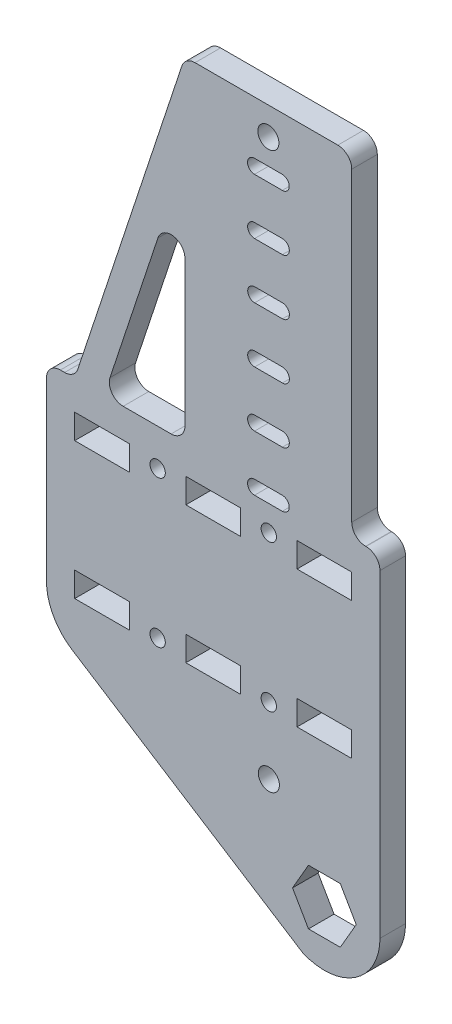
SolidWorks part; units mm, degrees
ref_plane "Front Plane" through (0, 0, 0) normal (0, 0, 1) x (1, 0, 0)
ref_plane "Top Plane" through (0, 0, 0) normal (0, 1, 0) x (1, 0, 0)
ref_plane "Right Plane" through (0, 0, 0) normal (1, 0, 0) x (0, 0, -1)
sketch "Sketch1" plane through (0, 0, 0) normal (0, 0, 1) x (1, 0, 0)
  line L0 (-38.1, 0) -> (38.1, 0) construction
  line L1 (31.65, -12.8) -> (19.15, -12.8)
  line L2 (38.1, -12.8) -> (38.1, 12.8)
  line L3 (31.65, 12.8) -> (19.15, 12.8)
  line L4 (-38.1, -12.8) -> (-38.1, 12.8)
  line L5 (38.1, -12.8) -> (-38.1, 12.8) construction
  line L6 (38.1, 12.8) -> (-38.1, -12.8) construction
  line L7 (6.25, 18.442) -> (-6.25, 18.442)
  line L8 (-19.15, -18.442) -> (-31.65, -12.8) construction
  line L9 (-19.15, -12.8) -> (-31.65, -18.442) construction
  line L10 (6.25, -12.8) -> (-6.25, -12.8)
  line L11 (-19.15, -12.8) -> (-31.65, -12.8)
  line L12 (31.65, -12.8) -> (31.65, -18.442)
  line L13 (19.15, -12.8) -> (19.15, -18.442)
  line L14 (12.6, 101.346) -> (12.6, 25.146) construction
  line L15 (-19.15, 12.8) -> (-19.15, 18.442)
  line L16 (-19.15, 18.442) -> (-31.65, 18.442)
  line L17 (-31.65, 12.8) -> (-31.65, 18.442)
  line L18 (-19.15, 12.8) -> (-31.65, 18.442) construction
  line L19 (-19.15, 18.442) -> (-31.65, 12.8) construction
  line L20 (-6.25, 12.8) -> (-6.25, 18.442)
  line L21 (6.25, 12.8) -> (6.25, 18.442)
  line L22 (31.65, 18.442) -> (19.15, 18.442)
  line L23 (19.15, 12.8) -> (19.15, 18.442)
  line L24 (31.65, 12.8) -> (31.65, 18.442)
  line L25 (-19.15, 12.8) -> (-31.65, 12.8)
  line L26 (6.25, 12.8) -> (-6.25, 12.8)
  line L27 (-38.1, 12.8) -> (-38.1, 25.146)
  line L28 (-38.1, 25.146) -> (-31.65, 25.146)
  line L29 (31.65, 25.146) -> (38.1, 25.146)
  line L30 (38.1, 25.146) -> (38.1, 12.8)
  line L31 (31.65, -18.442) -> (19.15, -18.442)
  line L32 (6.25, -12.8) -> (6.25, -18.442)
  line L33 (-6.25, -12.8) -> (-6.25, -18.442)
  line L34 (-31.65, -12.8) -> (-31.65, -18.442)
  line L35 (-19.15, -18.442) -> (-31.65, -18.442)
  line L36 (-19.15, -12.8) -> (-19.15, -18.442)
  line L37 (6.25, -18.442) -> (-6.25, -18.442)
  line L38 (31.65, -12.8) -> (19.15, -12.8)
  line L39 (-19.15, -12.8) -> (-31.65, -12.8)
  line L40 (6.25, -12.8) -> (-6.25, -12.8)
  line L41 (6.25, 12.8) -> (19.15, 12.8) construction
  line L42 (32.6746, -50.8) -> (29.0373, -44.5)
  line L43 (29.0373, -44.5) -> (21.7627, -44.5)
  line L44 (21.7627, -44.5) -> (18.1254, -50.8)
  line L45 (18.1254, -50.8) -> (21.7627, -57.1)
  line L46 (21.7627, -57.1) -> (29.0373, -57.1)
  line L47 (29.0373, -57.1) -> (32.6746, -50.8)
  line L48 (-6.25, 12.8) -> (-19.15, 12.8) construction
  line L49 (31.65, 25.146) -> (31.65, 101.346)
  line L50 (31.65, 101.346) -> (-6.45, 101.346)
  line L51 (-6.45, 101.346) -> (-31.65, 25.146)
  line L52 (-6.45, 81.122) -> (-6.45, 25.146)
  line L53 (-6.45, 25.146) -> (-24.9618, 25.146)
  line L54 (-6.45, 81.122) -> (-24.9618, 25.146)
  line L55 (-38.1, -12.8) -> (-38.1, -25.146)
  line L56 (-0.4211, 99.3522) -> (-25.6211, 23.1522) construction
  line L57 (-38.1, -25.146) -> (20.4722, -62.505)
  line L58 (38.1, -12.8) -> (38.1, -25.146)
  line L59 (38.1, -25.146) -> (38.1, -50.8)
  circle A0 centre (25.4, -50.8) radius 6.3 construction
  circle A1 centre (12.7, 16.7687) radius 1.7526
  circle A2 centre (-12.7, 16.7687) radius 1.7526
  circle A3 centre (12.7, -16.7687) radius 1.7526
  circle A4 centre (-12.7, -16.7687) radius 1.7526
  circle A5 centre (12.6, 94.996) radius 2.413
  arc A6 (20.4722, -62.505) -> (38.1, -50.8) centre (25.4, -50.8) ccw
  point P0 (0, 0)
  point P8 (-25.4, 15.621)
  point P37 (-25.4, -15.621)
  point P70 (-3.225, -28.575)
  dimension "D3" = 12.5
  dimension "D5" = 12.6
  dimension "D6" = 50.8
  dimension "D8" = 3.5052
  dimension "D13" = 3.5052
  dimension "D11" = 4.826
  dimension "D1" = 25.6
  dimension "D2" = 76.2
  dimension "D7" = 63.5
  dimension "D4" = 5.642
  dimension "D9" = 12.7
  dimension "D10" = 3
  dimension "D12" = 3.9688
  dimension "D14" = 3.9688
  dimension "D15" = 76.2
  dimension "D16" = 38.1
  dimension "D17" = 6.35
  dimension "D20" = 9.525
  dimension "D21" = 9.525
  dimension "D18" = 6.35
extrude "Boss-Extrude1" add sketch "Sketch1" along normal blind 5.842 contours L58 L2 L30 L29 L49 L50 L51 L28 L27 L4 L55 A4 L32 L37 L33 L10 L11 L36 L35 L34 L12 L31 L13 L1 L21 L26 L20 L7 L15 L25 L17 L16 L24 L3 L23 L22 L47 L46 L45 L44 region at (36.2839, -18.973, 0)
fillet "Fillet1" radius 3.175 4 edges at (-38.1, 25.146, 2.921) (38.1, 25.146, 2.921) (-31.65, 25.146, 2.921) (31.65, 25.146, 2.921)
fillet "Fillet2" radius 3.175 3 edges at (-6.45, 25.146, 2.921) (-6.45, 81.122, 2.921) (-24.9618, 25.146, 2.921)
fillet "Fillet3" radius 3.175 2 edges at (31.65, 101.346, 2.921) (-6.45, 101.346, 2.921)
sketch "Sketch2" plane through (0, 0, 5.842) normal (0, 0, 1) x (1, 0, 0)
  circle A0 centre (29.0373, -44.5) radius 0.1984
  circle A1 centre (32.6746, -50.8) radius 0.1984
  circle A2 centre (29.0373, -57.1) radius 0.1984
  circle A3 centre (21.7627, -57.1) radius 0.1984
  circle A4 centre (18.1254, -50.8) radius 0.1984
  circle A5 centre (21.7627, -44.5) radius 0.1984
  dimension "D1" = 0.3969
  dimension "D2" = 0.3969
  dimension "D3" = 0.3969
  dimension "D4" = 0.3969
  dimension "D5" = 0.3969
  dimension "D6" = 0.3969
extrude "Cut-Extrude1" [suppressed] cut sketch "Sketch2" against normal through all
sketch "Sketch3" plane through (0, 0, 5.842) normal (0, 0, 1) x (1, 0, 0)
  line L0 (12.6, 94.996) -> (12.7, -16.7687) construction
  circle A0 centre (12.7136, -32.004) radius 2.413
  dimension "D1" = 4.826
  dimension "D2" = 127
extrude "Cut-Extrude2" cut sketch "Sketch3" against normal through all
sketch "Sketch5" [suppressed] plane through (0, 0, 5.842) normal (0, 0, 1) x (1, 0, 0)
  line L1 (-55.0734, 111.0269) -> (34.825, 111.0269)
  line L2 (-55.0734, 111.0269) -> (-55.0734, 25.146)
  line L3 (-55.0734, 25.146) -> (34.825, 25.146)
  line L4 (34.825, 111.0269) -> (34.825, 25.146)
extrude "Cut-Extrude3" [suppressed] cut sketch "Sketch5" against normal through all
sketch "Sketch6" [suppressed] plane through (0, 0, 5.842) normal (0, 0, 1) x (1, 0, 0)
  line L0 (-34.925, 25.146) -> (34.925, 25.146) construction
  line L1 (31.4879, 25.146) -> (-22.4871, 25.146)
  line L2 (31.4879, 78.486) -> (34.6629, 74.676)
  line L3 (31.4879, 78.486) -> (-20.5821, 78.486)
  line L4 (-22.4871, 25.146) -> (-25.0279, 25.146)
  line L5 (34.6629, 25.146) -> (-22.4871, 78.486) construction
  line L6 (34.6629, 78.486) -> (-22.4871, 25.146) construction
  line L7 (6.0879, 25.146) -> (6.0879, 48.411) construction
  line L8 (-31.75, 25.146) -> (-22.4871, 51.816)
  line L9 (-38.1, -23.6461) -> (-38.1, 21.971) construction
  line L10 (34.6629, 74.676) -> (34.6629, 41.021)
  line L11 (-31.75, 25.146) -> (-25.0279, 25.146)
  line L12 (-22.4871, 51.816) -> (-22.4871, 71.3764)
  line L13 (31.4879, 70.866) -> (31.4879, 42.926) construction
  line L14 (31.4879, 37.846) -> (31.4879, 25.146)
  line L15 (31.4879, 37.846) -> (34.6629, 41.021)
  circle A0 centre (31.4879, 70.866) radius 1.651
  circle A1 centre (31.4879, 42.926) radius 1.651
  circle A2 centre (-20.5821, 74.676) radius 1.651
  circle A3 centre (-19.3121, 27.686) radius 1.651
  arc A4 (-20.5821, 78.486) -> (-22.4871, 71.3764) centre (-20.5821, 74.676) ccw
  point P0 (6.0879, 51.816)
  point P13 (-25.7515, 23.0626)
  point P14 (-16.4886, 49.7326)
  dimension "D5" = 3.302
  dimension "D6" = 3.302
  dimension "D9" = 12.7
  dimension "D10" = 3.302
  dimension "D12" = 3.302
  dimension "D1" = 53.34
  dimension "D2" = 57.15
  dimension "D3" = 6.35
  dimension "D7" = 49.53
  dimension "D8" = 27.94
  dimension "D11" = 52.07
  dimension "D13" = 50.8
  dimension "D14" = 15.24
  dimension "D4" = 7.62
extrude "Boss-Extrude3" [suppressed] add sketch "Sketch6" against normal up to surface (5.842 mm away) up to face at (15.1266, -32.004, 0)
fillet "Fillet6" [suppressed] radius 3.175
fillet "Fillet7" [suppressed] radius 1.5875
sketch "Sketch7" [suppressed] plane through (0, 0, 5.842) normal (0, 0, 1) x (1, 0, 0)
  line L0 (20.9561, 53.086) -> (-41.1495, 53.086) construction
  line L2 (5.0811, 78.486) -> (5.0811, 25.1147) construction
  line L3 (30.7443, 78.486) -> (-20.5821, 78.486) construction
  line L4 (5.0811, 65.786) -> (5.0811, 40.386) construction
  line L5 (8.2561, 65.786) -> (8.2561, 40.386)
  line L6 (1.9061, 65.786) -> (1.9061, 40.386)
  line L7 (17.7811, 65.786) -> (17.7811, 40.386) construction
  line L8 (20.9561, 65.786) -> (20.9561, 40.386)
  line L9 (14.6061, 65.786) -> (14.6061, 40.386)
  line L10 (-24.5007, 53.086) -> (20.9561, 53.086) construction
  line L11 (-7.6189, 65.786) -> (-7.6189, 40.386) construction
  line L12 (-10.7939, 65.786) -> (-10.7939, 40.386)
  line L13 (-4.4439, 65.786) -> (-4.4439, 40.386)
  arc A0 (8.2561, 65.786) -> (1.9061, 65.786) centre (5.0811, 65.786) ccw
  arc A1 (1.9061, 40.386) -> (8.2561, 40.386) centre (5.0811, 40.386) ccw
  arc A2 (20.9561, 65.786) -> (14.6061, 65.786) centre (17.7811, 65.786) ccw
  arc A3 (14.6061, 40.386) -> (20.9561, 40.386) centre (17.7811, 40.386) ccw
  arc A4 (-10.7939, 65.786) -> (-4.4439, 65.786) centre (-7.6189, 65.786) cw
  arc A5 (-4.4439, 40.386) -> (-10.7939, 40.386) centre (-7.6189, 40.386) cw
  point P10 (5.0811, 53.086)
  point P18 (17.7811, 53.086)
  point P26 (-7.6189, 53.086)
  dimension "D2" = 3.175
  dimension "D1" = 25.4
  dimension "D3" = 25.4
  dimension "D4" = 2
extrude "Cut-Extrude4" [suppressed] cut sketch "Sketch7" against normal through all
sketch "Sketch9" [suppressed] plane through (0, 0, 5.842) normal (0, 0, 1) x (1, 0, 0)
  line L0 (-38.1, -7.52) -> (38.1, -7.52) construction
  line L1 (-38.1, -23.6461) -> (-38.1, 21.971) construction
  line L2 (38.1, 21.971) -> (38.1, -17.5528) construction
  line L3 (-19.15, 12.8) -> (-31.65, 12.8) construction
  text T0 "SERGE" font "Roboto Condensed" height in points 42
  dimension "D1" = 20.32
extrude "Cut-Extrude5" [suppressed] cut sketch "Sketch9" against normal blind 0.3969
sketch "Sketch10" [suppressed] plane through (0, 0, 5.842) normal (0, 0, 1) x (1, 0, 0)
  line L0 (-38.1, -4.345) -> (38.1, -4.345) construction
  line L1 (-38.1, -23.6461) -> (-38.1, 21.971) construction
  line L2 (38.1, 21.971) -> (38.1, -17.5528) construction
  line L3 (-19.15, 12.8) -> (-31.65, 12.8) construction
  text T0 "SERGE" font "Bebas Neue" height in points 36
  dimension "D1" = 17.145
extrude "Cut-Extrude6" [suppressed] cut sketch "Sketch10" against normal blind 0.1984
sketch "Sketch11" plane through (0, 0, 5.842) normal (0, 0, 1) x (1, 0, 0)
  line L0 (12.6, 94.996) -> (12.7, 16.7687) construction
  line L1 (9.4669, 62.2324) -> (15.8169, 62.2324) construction
  line L2 (9.4669, 63.8199) -> (15.8169, 63.8199)
  line L3 (9.4669, 60.6449) -> (15.8169, 60.6449)
  line L4 (31.75, 55.8824) -> (-6.45, 55.8824) construction
  line L5 (-6.45, 61.4095) -> (-6.45, 28.321) construction
  line L6 (9.4506, 74.9324) -> (15.8006, 74.9324) construction
  line L7 (9.4506, 76.5199) -> (15.8006, 76.5199)
  line L8 (9.4506, 73.3449) -> (15.8006, 73.3449)
  line L9 (9.4344, 87.6324) -> (15.7844, 87.6324) construction
  line L10 (9.4344, 89.2199) -> (15.7844, 89.2199)
  line L11 (9.4344, 86.0449) -> (15.7844, 86.0449)
  line L12 (9.4344, 24.1324) -> (15.7844, 24.1324) construction
  line L13 (9.4344, 22.5449) -> (15.7844, 22.5449)
  line L14 (9.4344, 25.7199) -> (15.7844, 25.7199)
  line L15 (9.4506, 36.8324) -> (15.8006, 36.8324) construction
  line L16 (9.4506, 35.2449) -> (15.8006, 35.2449)
  line L17 (9.4506, 38.4199) -> (15.8006, 38.4199)
  line L18 (9.4669, 49.5324) -> (15.8169, 49.5324) construction
  line L19 (9.4669, 47.9449) -> (15.8169, 47.9449)
  line L20 (9.4669, 51.1199) -> (15.8169, 51.1199)
  arc A0 (9.4669, 63.8199) -> (9.4669, 60.6449) centre (9.4669, 62.2324) ccw
  arc A1 (15.8169, 60.6449) -> (15.8169, 63.8199) centre (15.8169, 62.2324) ccw
  arc A2 (9.4506, 76.5199) -> (9.4506, 73.3449) centre (9.4506, 74.9324) ccw
  arc A3 (15.8006, 73.3449) -> (15.8006, 76.5199) centre (15.8006, 74.9324) ccw
  arc A4 (9.4344, 89.2199) -> (9.4344, 86.0449) centre (9.4344, 87.6324) ccw
  arc A5 (15.7844, 86.0449) -> (15.7844, 89.2199) centre (15.7844, 87.6324) ccw
  arc A6 (9.4344, 22.5449) -> (9.4344, 25.7199) centre (9.4344, 24.1324) cw
  arc A7 (15.7844, 25.7199) -> (15.7844, 22.5449) centre (15.7844, 24.1324) cw
  arc A8 (9.4506, 35.2449) -> (9.4506, 38.4199) centre (9.4506, 36.8324) cw
  arc A9 (15.8006, 38.4199) -> (15.8006, 35.2449) centre (15.8006, 36.8324) cw
  arc A10 (9.4669, 47.9449) -> (9.4669, 51.1199) centre (9.4669, 49.5324) cw
  arc A11 (15.8169, 51.1199) -> (15.8169, 47.9449) centre (15.8169, 49.5324) cw
  point P6 (12.6419, 62.2324)
  point P16 (12.65, 55.8824)
  point P19 (12.6256, 74.9324)
  point P26 (12.6094, 87.6324)
  point P32 (12.6094, 24.1324)
  point P39 (12.6256, 36.8324)
  point P46 (12.6419, 49.5324)
  dimension "D1" = 1.5875
  dimension "D2" = 6.35
  dimension "D3" = 6.35
  dimension "D4" = 3
extrude "Cut-Extrude7" cut sketch "Sketch11" against normal through all
fillet "Fillet8" [suppressed] radius 25.4
fillet "Fillet9" radius 12.7 1 edges at (-38.1, -25.146, 2.921)
